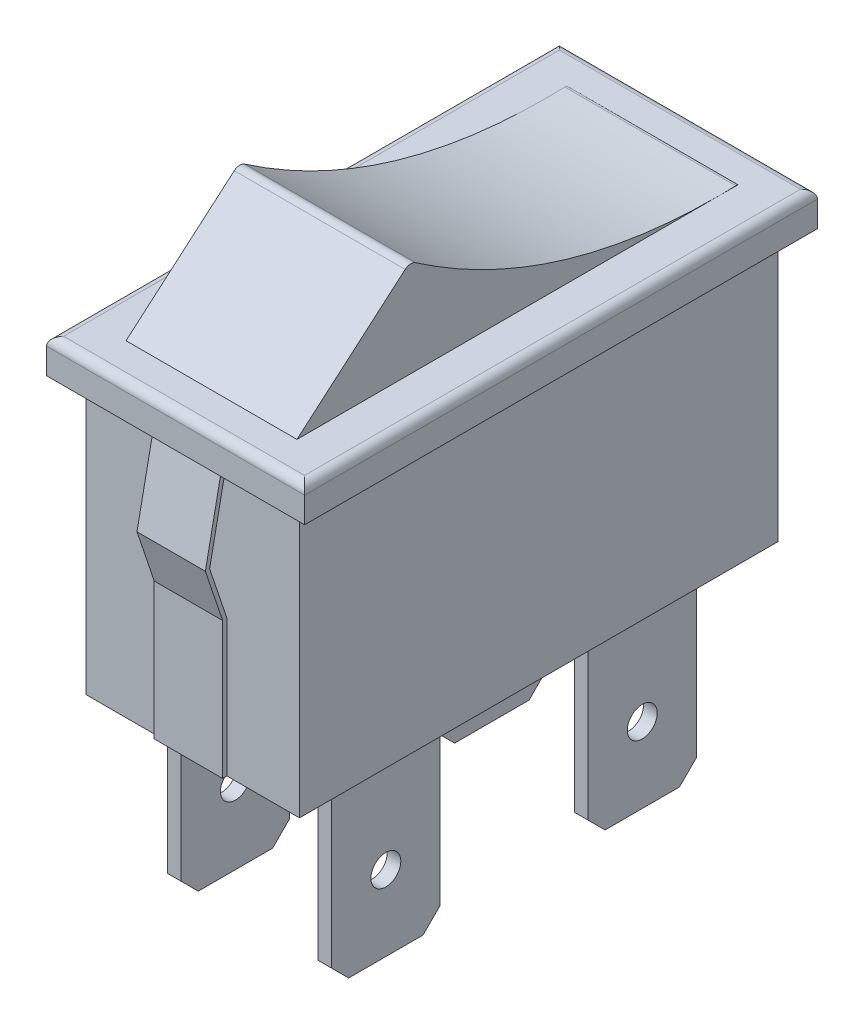
SolidWorks part; units mm, degrees
ref_plane "Front Plane" through (0, 0, 0) normal (0, 0, 1) x (1, 0, 0)
ref_plane "Top Plane" through (0, 0, 0) normal (0, 1, 0) x (1, 0, 0)
ref_plane "Right Plane" through (0, 0, 0) normal (1, 0, 0) x (0, 0, -1)
sketch "Sketch1" plane through (0, 0, 0) normal (0, 1, 0) x (1, 0, 0)
  line L1 (-6.25, -14) -> (6.25, -14)
  line L2 (-6.25, -14) -> (-6.25, 14)
  line L3 (-6.25, 14) -> (6.25, 14)
  line L4 (6.25, -14) -> (6.25, 14)
  line L5 (-6.25, -14) -> (6.25, 14) construction
  line L6 (-6.25, 14) -> (6.25, -14) construction
  point P0 (0, 0)
  dimension "D1" = 12.5
  dimension "D2" = 28
extrude "Boss-Extrude1" add sketch "Sketch1" along normal blind 16
sketch "Sketch2" plane through (0, 16, 0) normal (0, 1, 0) x (1, 0, 0)
  line L1 (-7.55, -15) -> (7.55, -15)
  line L2 (-7.55, -15) -> (-7.55, 15)
  line L3 (-7.55, 15) -> (7.55, 15)
  line L4 (7.55, -15) -> (7.55, 15)
  line L5 (-7.55, -15) -> (7.55, 15) construction
  line L6 (-7.55, 15) -> (7.55, -15) construction
  point P0 (0, 0)
  dimension "D1" = 30
  dimension "D2" = 15.1
extrude "Boss-Extrude2" add sketch "Sketch2" along normal blind 2
fillet "Fillet1" radius 0.5 4 edges at (0, 18, 15) (-7.55, 18, 0) (0, 18, -15) (7.55, 18, 0)
sketch "Sketch3" plane through (0, 18, 0) normal (0, 1, 0) x (1, 0, 0)
  line L1 (-5, -12.9) -> (5, -12.9)
  line L2 (-5, -12.9) -> (-5, 12.9)
  line L3 (-5, 12.9) -> (5, 12.9)
  line L4 (5, -12.9) -> (5, 12.9)
  line L5 (-5, -12.9) -> (5, 12.9) construction
  line L6 (-5, 12.9) -> (5, -12.9) construction
  point P0 (0, 0)
  dimension "D1" = 25.8
  dimension "D2" = 10
extrude "Boss-Extrude3" add sketch "Sketch3" along normal blind 5.7
sketch "Sketch4" plane through (5, 0, 0) normal (1, 0, 0) x (0, 0, -1)
  line L0 (-12.9, 18) -> (12.9, 18) construction
  line L1 (-12.9, 23.7) -> (12.9, 23.7) construction
  line L2 (12.9, 23.7) -> (12.9, 18) construction
  line L3 (-12.9, 18) -> (-6.2773, 23.7)
  line L4 (-12.9, 23.7) -> (-12.9, 18) construction
  spline S0 degree 2 poles (-6.2773, 23.7) (2.3454, 17.6405) (12.9, 18.0227) knots 0 0 0 1 1 1
  line M4 (12.9, 18) -> (12.9, 23.7)
  line M5 (12.9, 23.7) -> (-12.9, 23.7)
  line M6 (-12.9, 23.7) -> (-12.9, 18)
  dimension "D1" = 20
extrude "Cut-Extrude1" cut sketch "Sketch4" against normal through all and the other way through all contours L3 M6 M5 | S0 M5 M4 region at (5, 21.8, 10.6924) region at (5, 21.3437, -5.5189)
fillet "Fillet2" radius 0.5 1 edges at (0, 23.7, 6.2773)
fillet "Fillet3" radius 0.4 1 edges at (0, 18.0227, -12.9)
sketch "Sketch8" plane through (0, 0, 0) normal (1, 0, 0) x (0, 0, -1)
  line L0 (0, 5.9179) -> (0, -5.9179) construction
  line L1 (-14, 16) -> (-14.25, 16)
  line L2 (-15.0091, 11) -> (-14, 16)
  line L3 (-14, 8) -> (-15.0091, 11)
  line L4 (14.25, 0) -> (14.25, 8)
  line L5 (-15.2591, 11) -> (-14.25, 16)
  line L6 (-14, 8) -> (-14, 0)
  line L7 (14, 8) -> (14, 0)
  line L8 (14, 16) -> (14, 0) construction
  line L9 (-14.25, 8) -> (-15.2591, 11)
  line L10 (14, 0) -> (14.25, 0)
  line L11 (14.25, 8) -> (15.2591, 11)
  line L12 (15.2591, 11) -> (14.25, 16)
  line L13 (14, 8) -> (15.0091, 11)
  line L14 (15.0091, 11) -> (14, 16)
  line L15 (14, 16) -> (14.25, 16)
  line L16 (-14, 0) -> (-14.25, 0)
  line L17 (-15, 16) -> (15, 16) construction
  line L18 (-14.25, 0) -> (-14.25, 8)
  line L19 (-14, 16) -> (-14, 0) construction
  line L20 (-14, 0) -> (14, 0) construction
  dimension "D1" = 0.25
  dimension "D2" = 8
  dimension "D3" = 150
  dimension "D4" = 5
extrude "Boss-Extrude4" add sketch "Sketch8" along normal blind 2 and the other way blind 2 separate body
sketch "Sketch9" plane through (0, 0, 0) normal (0, -1, 0) x (1, 0, 0)
  line L0 (0, 14) -> (0, -14) construction
  line L1 (-4.8, 10.675) -> (-4, 10.675)
  line L2 (-4.8, 10.675) -> (-4.8, 4.325)
  line L3 (-4.8, 4.325) -> (-4, 4.325)
  line L4 (-4, 10.675) -> (-4, 4.325)
  line L5 (-4.8, -4.325) -> (-4, -4.325)
  line L6 (-4.8, -4.325) -> (-4.8, -10.675)
  line L7 (-4.8, -10.675) -> (-4, -10.675)
  line L8 (-4, -4.325) -> (-4, -10.675)
  line L9 (-6.25, 14) -> (6.25, 14) construction
  line L10 (-2, -14) -> (2, -14) construction
  line L11 (4, -4.325) -> (4, -10.675)
  line L12 (4.8, -10.675) -> (4, -10.675)
  line L13 (4.8, -4.325) -> (4.8, -10.675)
  line L14 (4.8, -4.325) -> (4, -4.325)
  line L15 (4, 10.675) -> (4, 4.325)
  line L16 (4.8, 4.325) -> (4, 4.325)
  line L17 (4.8, 10.675) -> (4.8, 4.325)
  line L18 (4.8, 10.675) -> (4, 10.675)
  line L19 (0, 0) -> (3.3, 0) construction
  line L20 (-4, 7.5) -> (4, 7.5) construction
  line L21 (-4, -7.5) -> (4, -7.5) construction
  dimension "D1" = 0.8
  dimension "D2" = 6.35
  dimension "D3" = 6.35
  dimension "D4" = 0.8
  dimension "D5" = 4
  dimension "D7" = 7.5
  dimension "D8" = 7.5
extrude "Boss-Extrude5" add sketch "Sketch9" along normal blind 11
chamfer "Chamfer1" distance 1 angle 45 8 edges at (-4.4, -11, -4.325) (-4.4, -11, -10.675) (4.4, -11, -10.675) (4.4, -11, -4.325) (4.4, -11, 4.325) (4.4, -11, 10.675) (-4.4, -11, 4.325) (-4.4, -11, 10.675)
sketch "Sketch10" plane through (4.8, 0, 0) normal (1, 0, 0) x (0, 0, -1)
  line L0 (0, 0) -> (0, -2.5809) construction
  line L1 (-5.325, -11) -> (-9.675, -11) construction
  circle A0 centre (-7.5, -6.6) radius 0.875
  circle A1 centre (7.5, -6.6) radius 0.875
  dimension "D1" = 1.75
  dimension "D2" = 4.4
  dimension "D4" = 7.5
extrude "Cut-Extrude2" cut sketch "Sketch10" against normal through all
